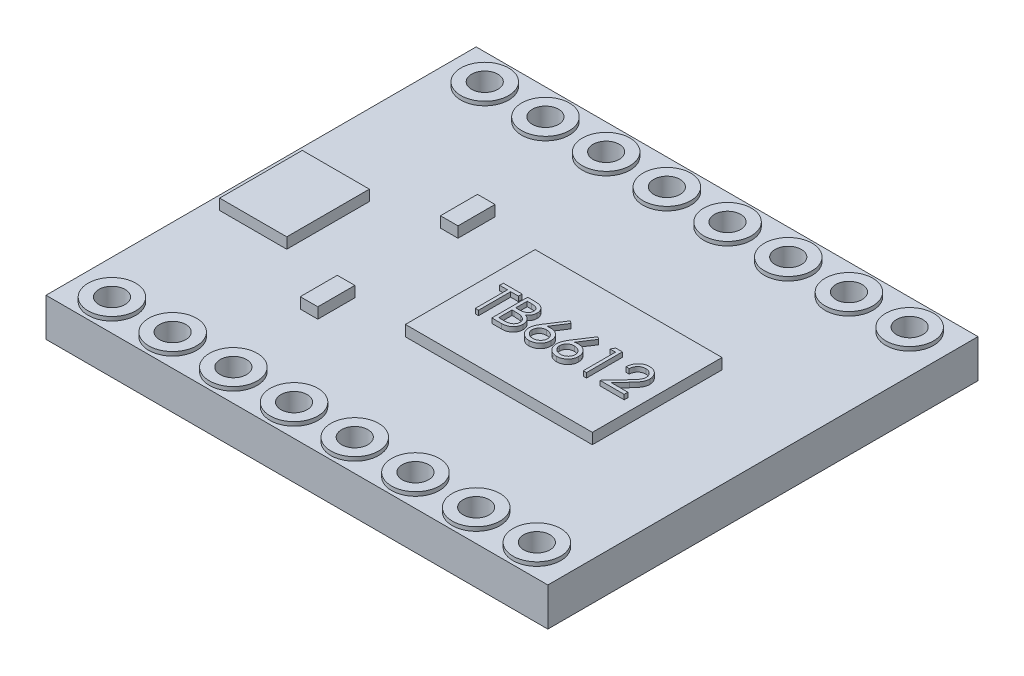
SolidWorks part; units mm, degrees
note: The reader was unsure of these and kept them because the rebuilt part matched: shared geometry of "Sketch1<4>", "Sketch1<6>".
ref_plane "Front Plane" through (0, 0, 0) normal (0, 0, 1) x (1, 0, 0)
ref_plane "Top Plane" through (0, 0, 0) normal (0, 1, 0) x (1, 0, 0)
ref_plane "Right Plane" through (0, 0, 0) normal (1, 0, 0) x (0, 0, -1)
sketch "Sketch1" plane through (0, 0, 0) normal (0, 1, 0) x (1, 0, 0)
  line L0 (51.1383, 73.9819) -> (72.1383, 73.9819) construction
  line L2 (51.2056, 92.061) -> (72.2056, 92.061)
  line L3 (51.2056, 92.061) -> (51.2056, 74.061)
  line L4 (51.2056, 74.061) -> (72.2056, 74.061)
  line L5 (72.2056, 92.061) -> (72.2056, 74.061)
  line L6 (60.2336, 85.4998) -> (68.0556, 85.4998)
  line L7 (60.2336, 85.4998) -> (60.2336, 80.0731)
  line L8 (60.2336, 80.0731) -> (68.0556, 80.0731)
  line L9 (68.0556, 85.4998) -> (68.0556, 80.0731)
  line L10 (51.7688, 84.2217) -> (54.5764, 84.2217)
  line L11 (51.7688, 84.2217) -> (51.7688, 80.7646)
  line L12 (51.7688, 80.7646) -> (54.5764, 80.7646)
  line L13 (54.5764, 84.2217) -> (54.5764, 80.7646)
  line L14 (57.0278, 86.296) -> (57.7612, 86.296)
  line L15 (57.0278, 86.296) -> (57.0278, 84.7455)
  line L16 (57.0278, 84.7455) -> (57.7612, 84.7455)
  line L17 (57.7612, 86.296) -> (57.7612, 84.7455)
  line L18 (57.0278, 80.4293) -> (57.7612, 80.4293)
  line L19 (57.0278, 80.4293) -> (57.0278, 78.8788)
  line L20 (57.0278, 78.8788) -> (57.7612, 78.8788)
  line L21 (57.7612, 80.4293) -> (57.7612, 78.8788)
  circle A0 centre (52.8156, 90.811) radius 0.55
  circle A1 centre (55.3556, 90.811) radius 0.55
  circle A2 centre (57.8956, 90.811) radius 0.55
  circle A3 centre (60.4356, 90.811) radius 0.55
  circle A4 centre (62.9756, 90.811) radius 0.55
  circle A5 centre (65.5156, 90.811) radius 0.55
  circle A6 centre (68.0556, 90.811) radius 0.55
  circle A7 centre (70.5956, 90.811) radius 0.55
  circle A8 centre (55.3556, 75.211) radius 0.55
  circle A9 centre (57.8956, 75.211) radius 0.55
  circle A10 centre (60.4356, 75.211) radius 0.55
  circle A11 centre (62.9756, 75.211) radius 0.55
  circle A12 centre (65.5156, 75.211) radius 0.55
  circle A13 centre (68.0556, 75.211) radius 0.55
  circle A14 centre (70.5956, 75.211) radius 0.55
  circle A15 centre (52.8156, 75.211) radius 0.55
  circle A16 centre (52.8156, 90.811) radius 1
  circle A17 centre (55.3556, 90.811) radius 1
  circle A18 centre (57.8956, 90.811) radius 1
  circle A19 centre (60.4356, 90.811) radius 1
  circle A20 centre (62.9756, 90.811) radius 1
  circle A21 centre (65.5156, 90.811) radius 1
  circle A22 centre (68.0556, 90.811) radius 1
  circle A23 centre (70.5956, 90.811) radius 1
  circle A24 centre (55.3556, 75.211) radius 1
  circle A25 centre (57.8956, 75.211) radius 1
  circle A26 centre (60.4356, 75.211) radius 1
  circle A27 centre (62.9756, 75.211) radius 1
  circle A28 centre (65.5156, 75.211) radius 1
  circle A29 centre (68.0556, 75.211) radius 1
  circle A30 centre (70.5956, 75.211) radius 1
  circle A31 centre (52.8156, 75.211) radius 1
  dimension "D4" = 1.1
  dimension "D9" = 8
  dimension "D1" = 21
  dimension "D2" = 21
  dimension "D3" = 18
  dimension "D5" = 1.61
  dimension "D6" = 1.25
  dimension "D7" = 8
  dimension "D8" = 2
  dimension "D10" = 2
extrude "Boss-Extrude1" add sketch "Sketch1" along normal blind 1.6 contours L5 L2 L3 L4 A15 A14 A13 A12 A11 A10 A9 A8 A7 A6 A5 A4 A3 A2 A1 A0 L6 L9 L8 L7 L10 L13 L12 L11 L14 L17 L16 L15
extrude "Boss-Extrude2" add sketch "Sketch1<4>" along normal blind 2.05 contours L17 L14 L15 L16 | L13 L10 L11 L12 | L21 L18 L19 L20 | L9 L6 L7 L8
sketch "Sketch1<4>" plane through (0, 0, 0) normal (0, 1, 0) x (1, 0, 0) same geometry as "Sketch1"
sketch "Sketch3" plane through (0, 2.05, 0) normal (0, 1, 0) x (1, 0, 0)
  text T0 "TB6612" font "Century Gothic" height 1.5
extrude "Boss-Extrude3" add sketch "Sketch3" along normal blind 0.2
extrude "Boss-Extrude4" add sketch "Sketch1<6>" along normal blind 1.7663 contours A16 A0 | A17 A1 | A18 A2 | A19 A3 | A20 A4 | A21 A5 | A22 A6 | A23 A7 | A30 A14 | A29 A13 | A28 A12 | A27 A11 | A26 A10 | A25 A9 | A31 A15 | A24 A8
sketch "Sketch1<6>" plane through (0, 0, 0) normal (0, 1, 0) x (1, 0, 0) same geometry as "Sketch1"
